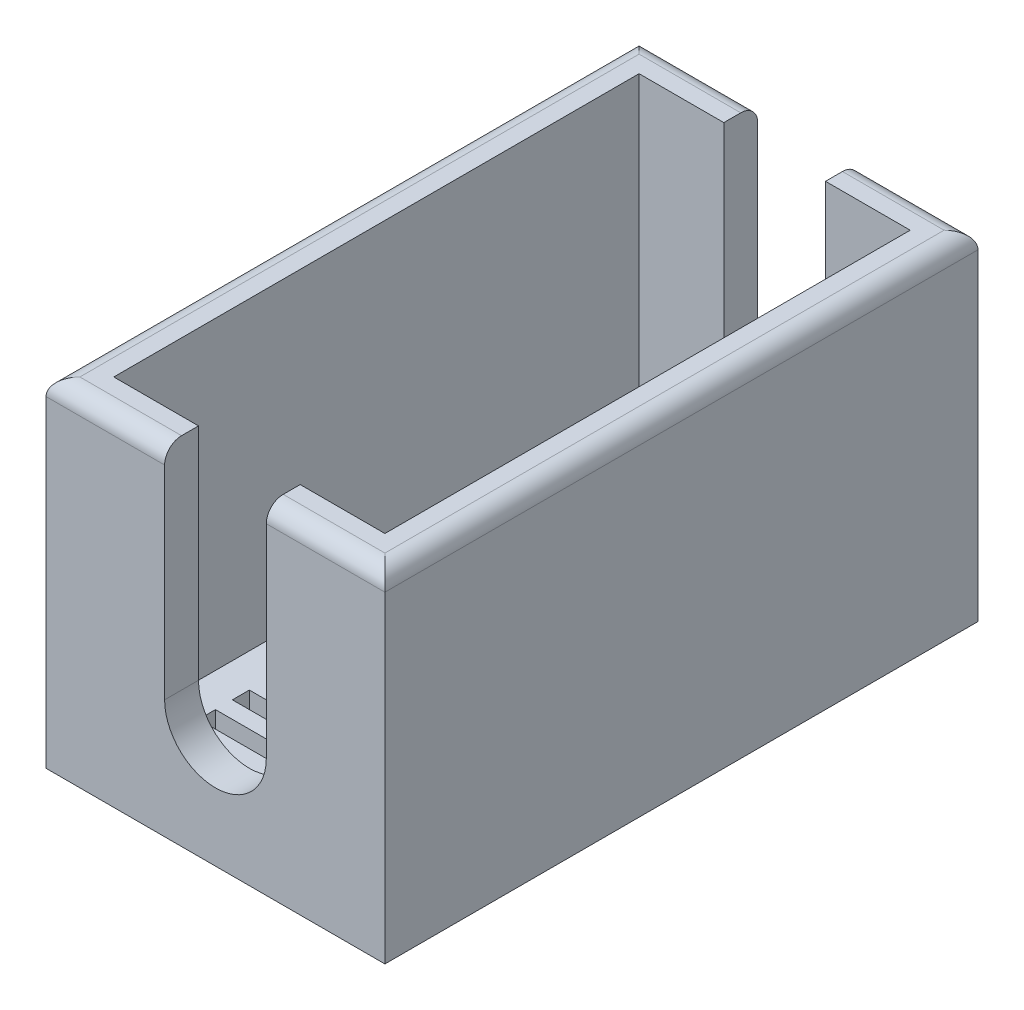
SolidWorks part; units mm, degrees
ref_plane "Ebene vorne" through (0, 0, 0) normal (0, 0, 1) x (1, 0, 0)
ref_plane "Ebene oben" through (0, 0, 0) normal (0, 1, 0) x (1, 0, 0)
ref_plane "Ebene rechts" through (0, 0, 0) normal (1, 0, 0) x (0, 0, -1)
sketch "Skizze1" plane through (0, 0, 0) normal (0, 0, 1) x (1, 0, 0)
  line L1 (0, 0) -> (20, 0)
  line L2 (0, 0) -> (0, 20)
  line L3 (0, 20) -> (20, 20)
  line L4 (20, 0) -> (20, 20)
  dimension "D1" = 20
  dimension "D2" = 20
extrude "Aufsatz-Linear austragen1" add sketch "Skizze1" along normal blind 35
shell "Wandung1" thickness 2 removed face at (10, 20, 17.5)
sketch "Skizze3" plane through (0, 0, 35) normal (0, 0, 1) x (1, 0, 0)
  line L0 (10, 20) -> (10, 7) construction
  line L1 (20, 20) -> (0, 20) construction
  line L2 (13, 20) -> (13, 7)
  line L3 (7, 20) -> (7, 7)
  arc A0 (13, 20) -> (7, 20) centre (10, 20) ccw
  arc A1 (7, 7) -> (13, 7) centre (10, 7) ccw
  point P4 (10, 13.5)
  dimension "D2" = 13
  dimension "D1" = 3
extrude "Schnitt-Linear austragen2" cut sketch "Skizze3" against normal up to surface (2 mm away) up to face at (10, 11, 33)
ref_plane "Ebene1" through (0, 0, 17.5) normal (0, 0, 1) x (1, 0, 0)
mirror "Spiegeln1" about plane through (0, 0, 17.5) normal (0, 0, 1) of "Schnitt-Linear austragen2"
fillet "Verrundung1" radius 1 6 edges at (16.5, 20, 35) (3.5, 20, 35) (16.5, 20, 0) (3.5, 20, 0) (0, 20, 17.5) (20, 20, 17.5)
sketch "Skizze4" plane through (0, 2, 0) normal (0, 1, 0) x (1, 0, 0)
  line L1 (16, -18) -> (4, -18)
  line L2 (16, -18) -> (16, -17)
  line L3 (16, -17) -> (4, -17)
  line L4 (4, -18) -> (4, -17)
  line L6 (18, -33) -> (18, -2) construction
  line L7 (2, -33) -> (18, -33) construction
  point P6 (16, -17.5)
  dimension "D1" = 1
  dimension "D2" = 12
  dimension "D3" = 2
  dimension "D4" = 15.5
extrude "Schnitt-Linear austragen3" cut sketch "Skizze4" against normal up to surface (2 mm away) up to face at (10, 0, 17.5)
pattern_linear "Lineares Muster1" count 8 spacing 2 along (0, 0, 1) count 8 spacing 2 along (0, 0, -1) of "Schnitt-Linear austragen3"
sketch "Skizze5" plane through (0, 0, 0) normal (0, -1, 0) x (1, 0, 0)
  line L0 (10.45, 17.5) -> (-10.45, 17.5) construction
  line L1 (16, 10) -> (4, 10)
  line L2 (16, 10) -> (16, 25)
  line L3 (16, 25) -> (4, 25)
  line L4 (4, 10) -> (4, 25)
  line L5 (16, 10) -> (4, 25) construction
  line L6 (16, 25) -> (4, 10) construction
  point P0 (10, 17.5)
  dimension "D1" = 15
extrude "Aufsatz-Linear austragen2" add sketch "Skizze5" against normal up to surface (2 mm away) up to face at (10, 2, 3.5)
